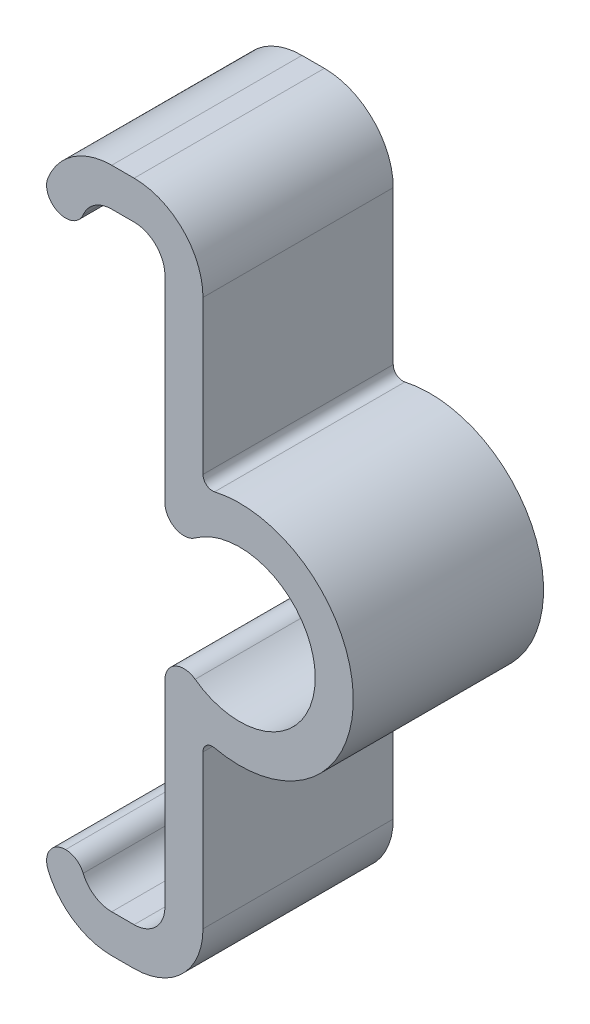
SolidWorks part; units mm, degrees
ref_plane "Front Plane" through (0, 0, 0) normal (0, 0, 1) x (1, 0, 0)
ref_plane "Top Plane" through (0, 0, 0) normal (0, 1, 0) x (1, 0, 0)
ref_plane "Right Plane" through (0, 0, 0) normal (1, 0, 0) x (0, 0, -1)
sketch "Sketch1" plane through (0, 0, 0) normal (0, 0, 1) x (1, 0, 0)
  line L0 (-4.318, -11.285) -> (-4.318, -14.37) construction
  line L1 (-2.748, -15.94) -> (-1.57, -15.94) construction
  line L2 (0, -14.37) -> (0, 14.37) construction
  line L3 (-1.57, 15.94) -> (-2.748, 15.94) construction
  line L4 (-4.318, 14.37) -> (-4.318, 11.285) construction
  line L5 (-4.368, -11.285) -> (-4.368, -14.37)
  line L6 (-2.748, -15.99) -> (-1.57, -15.99)
  line L7 (0.05, -14.37) -> (0.05, 14.37)
  line L8 (-1.57, 15.99) -> (-2.748, 15.99)
  line L9 (-4.368, 14.37) -> (-4.368, 11.285)
  line L10 (-6.368, -11.285) -> (-6.368, -14.37)
  line L11 (-2.748, -17.99) -> (-1.57, -17.99)
  line L12 (2.05, -14.37) -> (2.05, 14.37)
  line L13 (-1.57, 17.99) -> (-2.748, 17.99)
  line L14 (-6.368, 14.37) -> (-6.368, 11.285)
  line L15 (-4.368, 14.37) -> (-6.368, 14.37)
  line L16 (-4.368, -14.37) -> (-6.368, -14.37)
  arc A0 (-4.318, -14.37) -> (-2.748, -15.94) centre (-2.748, -14.37) ccw construction
  arc A1 (-1.57, -15.94) -> (0, -14.37) centre (-1.57, -14.37) ccw construction
  arc A2 (0, 14.37) -> (-1.57, 15.94) centre (-1.57, 14.37) ccw construction
  arc A3 (-2.748, 15.94) -> (-4.318, 14.37) centre (-2.748, 14.37) ccw construction
  arc A4 (-4.368, -14.37) -> (-2.748, -15.99) centre (-2.748, -14.37) ccw
  arc A5 (-1.57, -15.99) -> (0.05, -14.37) centre (-1.57, -14.37) ccw
  arc A6 (0.05, 14.37) -> (-1.57, 15.99) centre (-1.57, 14.37) ccw
  arc A7 (-2.748, 15.99) -> (-4.368, 14.37) centre (-2.748, 14.37) ccw
  circle A8 centre (3.975, 0) radius 3.975
  circle A9 centre (3.975, 0) radius 5.975
  arc A10 (-6.368, -14.37) -> (-2.748, -17.99) centre (-2.748, -14.37) ccw
  arc A11 (-1.57, -17.99) -> (2.05, -14.37) centre (-1.57, -14.37) ccw
  arc A12 (2.05, 14.37) -> (-1.57, 17.99) centre (-1.57, 14.37) ccw
  arc A13 (-2.748, 17.99) -> (-6.368, 14.37) centre (-2.748, 14.37) ccw
  dimension "D2" = 7.95
  dimension "D3" = 3.975
  dimension "D1" = 0.05
  dimension "D4" = 2
  dimension "D5" = 2
extrude "Boss-Extrude1" add sketch "Sketch1" along normal blind 10 contours L13 A13 L15 A7 L8 A6 L7 A9 L12 A12 | L12 A9 L7 A8 | L12 A9 A8 | L7 A9 L12 A8 | L11 A11 L12 A9 L7 A5 L6 A4 L16 A10 region at (-2.159, -16.149, 0) region at (0.9657, -3.7638, 0) region at (0.9657, 3.7638, 0) region at (0.209, 9.4375, 0) region at (2.1933, -4.5671, 0)
fillet "Fillet1" radius 1 2 edges at (0.05, -0.6285, 5) (0.05, 0.6285, 5)
fillet "Fillet2" radius 0.5 2 edges at (2.05, -5.6564, 5) (2.05, 5.6564, 5)
fillet "Fillet3" radius 1 4 edges at (-6.368, 14.37, 5) (-4.368, 14.37, 5) (-6.368, -14.37, 5) (-4.368, -14.37, 5)
equation "\"D3@Sketch1\"=\"D2@Sketch1\"/2"
